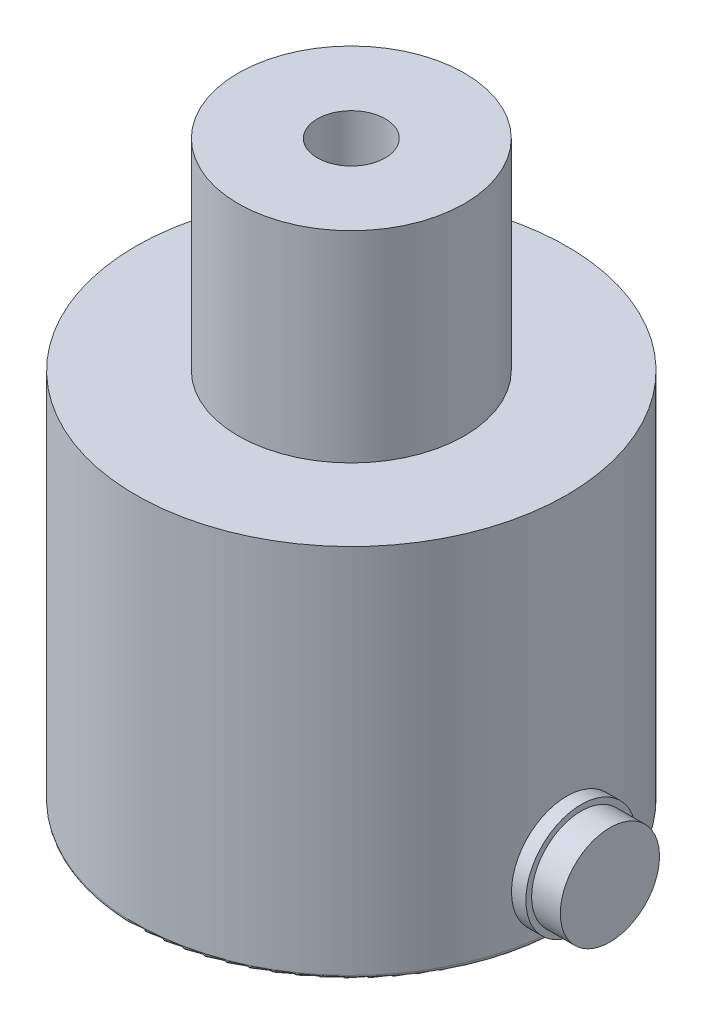
SolidWorks part; units mm, degrees
ref_plane "Front Plane" through (0, 0, 0) normal (0, 0, 1) x (1, 0, 0)
ref_plane "Top Plane" through (0, 0, 0) normal (0, 1, 0) x (1, 0, 0)
ref_plane "Right Plane" through (0, 0, 0) normal (1, 0, 0) x (0, 0, -1)
sketch "Sketch1" plane through (0, 0, 0) normal (0, 0, 1) x (1, 0, 0)
  line L1 (-19.05, 16.61) -> (-17, 16.61) construction
  line L2 (-19.05, 16.61) -> (-19.05, -16.61) construction
  line L4 (19.05, 16.61) -> (19.05, -16.2195)
  line L5 (-19.05, 16.61) -> (19.05, -16.61) construction
  line L6 (-19.05, -16.61) -> (19.05, 16.61) construction
  line L10 (-10, 21.65) -> (-10, 34.39) construction
  line L12 (10, 34.39) -> (10, 21.65)
  line L14 (0, -16.61) -> (0, 0)
  line L15 (0, 0) -> (0, 21.69)
  line L16 (19.05, -6.4405) -> (20.32, -6.4405)
  line L17 (20.32, -6.4405) -> (20.32, -16.2195)
  line L18 (20.32, -16.2195) -> (19.05, -16.2195)
  line L23 (19.05, -16.2195) -> (19.05, -6.4405)
  line L24 (0, -16.61) -> (-19.05, -16.61) construction
  line L25 (0, -16.61) -> (18.6595, -16.61)
  line L26 (10, 34.39) -> (3, 34.39)
  line L27 (-10, 34.39) -> (-3, 34.39) construction
  line L28 (20.32, -6.9485) -> (22.86, -6.9485)
  line L29 (10, 16.61) -> (0, 16.61) construction
  line L30 (0, 16.61) -> (-17, 16.61) construction
  line L31 (22.86, -6.9485) -> (22.86, -15.7115)
  line L32 (22.86, -15.7115) -> (20.32, -15.7115)
  line L33 (20.32, -15.7115) -> (20.32, -12.0964)
  line L34 (20.32, -12.0964) -> (20.32, -6.9485)
  line L35 (19.05, -11.33) -> (22.86, -11.33)
  line L36 (22.86, -7.2025) -> (1516.38, -7.2025)
  line L37 (1516.38, -7.2025) -> (1516.38, -15.4575)
  line L38 (1516.38, -15.4575) -> (22.86, -15.4575)
  line L39 (22.86, -7.2025) -> (22.86, -15.4575)
  line L40 (3, 34.39) -> (3, 21.69)
  line L41 (3, 21.69) -> (0, 21.69)
  line L42 (-3, 34.39) -> (-3, 21.69) construction
  line L43 (-3, 21.69) -> (0, 21.69) construction
  line L44 (10, 21.65) -> (10, 16.61)
  line L46 (-10, 16.61) -> (-17, 16.61) construction
  line L47 (-10, 21.65) -> (-10, 16.61) construction
  line L48 (10, 16.61) -> (19.05, 16.61)
  arc A0 (18.6595, -16.61) -> (19.05, -16.2195) centre (18.6595, -16.2195) ccw
  point P0 (0, 0)
  point P32 (19.685, -6.4405)
  dimension "D1" = 38.1
  dimension "D6" = 51
  dimension "D4" = 20
  dimension "D5" = 1.27
  dimension "D8" = 0.508
  dimension "D9" = 0.508
  dimension "D10" = 2.54
  dimension "D11" = 8.255
  dimension "D12" = 0.254
  dimension "D13" = 0.254
  dimension "D14" = 1493.52
  dimension "D15" = 6
  dimension "D3" = 12.7
  dimension "D2" = 5.08
  dimension "D7" = 27.94
revolve "Revolve1" add sketch "Sketch1" angle 360 about L15 region at (8.8789, 4.4868, 0)
revolve "Revolve2" add sketch "Sketch1<3>" angle 360 about L35 region at (19.685, -8.8852, 0) region at (21.59, -9.1392, 0)
sketch "Sketch1<3>" plane through (0, 0, 0) normal (0, 0, 1) x (1, 0, 0) same geometry as "Sketch1"
equation "\"EncoderOuterDiameter\"=1.5"
equation "\"D1@Sketch1\"=\"EncoderOuterDiameter\""
equation "\"ShaftDiameter\"= 12mm"
equation "\"PendulumDiameter\"=12mm"
equation "\"EncoderShaftDiameter\"= 6mm"
equation "\"EncoderShaftLength\"=15mm+.5in+3mm"
equation "\"EncoderCableDiameter\"=0.325"
equation "\"D11@Sketch1\"=\"EncoderCableDiameter\""
equation "\"EncoderCableLength\"=58.8"
equation "\"D14@Sketch1\"=\"EncoderCableLength\""
